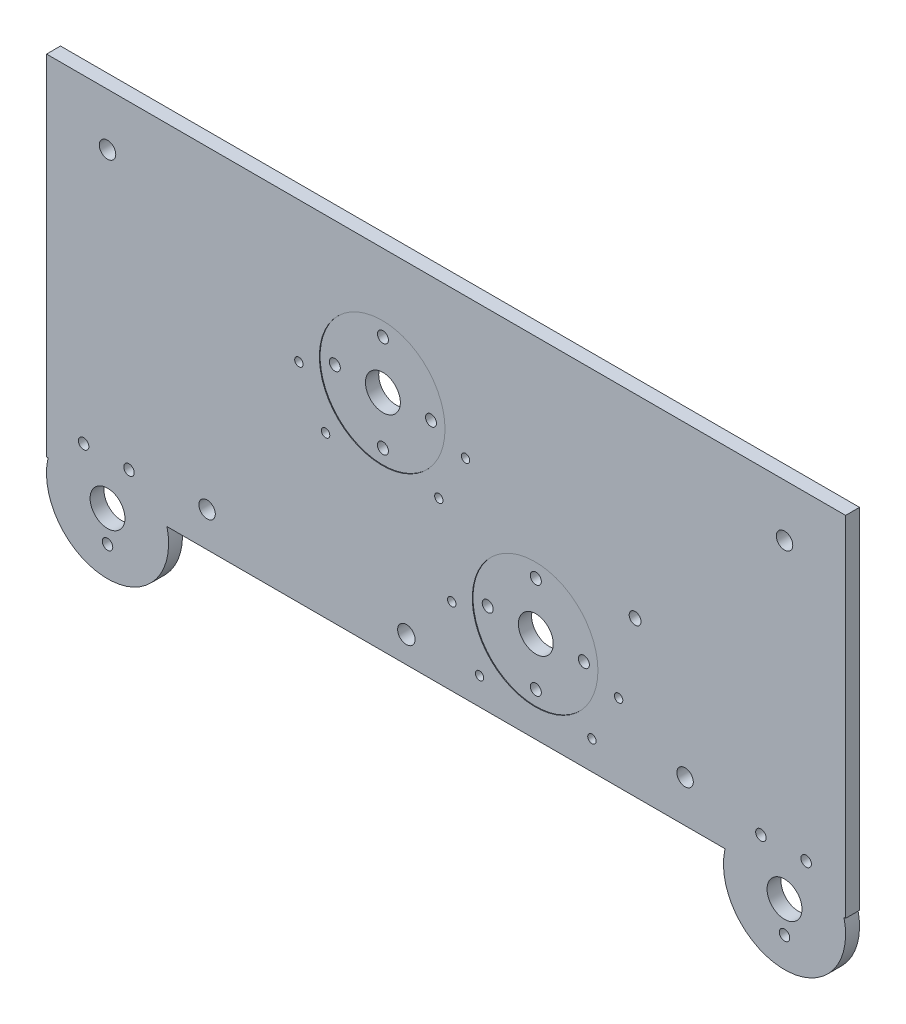
SolidWorks part; units mm, degrees
ref_plane "Front Plane" through (0, 0, 0) normal (0, 0, 1) x (1, 0, 0)
ref_plane "Top Plane" through (0, 0, 0) normal (0, 1, 0) x (1, 0, 0)
ref_plane "Right Plane" through (0, 0, 0) normal (1, 0, 0) x (0, 0, -1)
sketch "Sketch2" plane through (0, 0, 0) normal (0, 0, 1) x (1, 0, 0)
  line L1 (-143.383, -31.75) -> (143.383, -31.75)
  line L2 (-143.383, -31.75) -> (-143.383, 31.75)
  line L3 (-143.383, 31.75) -> (143.383, 31.75)
  line L4 (143.383, -31.75) -> (143.383, 31.75)
  line L5 (-143.383, -31.75) -> (143.383, 31.75) construction
  line L6 (-143.383, 31.75) -> (143.383, -31.75) construction
  line L16 (-143.383, 31.75) -> (143.383, 31.75)
  line L17 (-143.383, 31.75) -> (-143.383, 95.25)
  line L18 (-143.383, 95.25) -> (143.383, 95.25)
  line L19 (143.383, 31.75) -> (143.383, 95.25)
  circle A0 centre (-123.317, -36.83) radius 6.35
  circle A1 centre (123.063, -36.83) radius 6.35
  point P0 (0, 0)
  dimension "D3" = 20.066
  dimension "D5" = 5.08
  dimension "D7" = 63.5
  dimension "D4" = 12.7
  dimension "D1" = 63.5
  dimension "D2" = 286.766
  dimension "D6" = 20.32
extrude "Boss-Extrude1" add sketch "Sketch2" against normal blind 5.0749 contours A1 L1 L4 L3 L2 A0 | L3 L19 L18 L17 region at (0.0001, 0.0226, 0) region at (0, 63.5, 0)
ref_plane "Plane1" through (-143.383, 95.25, 0) normal (0, 1, 0) x (1, 0, 0)
ref_plane "Plane2" through (0, 0, -5.0749) normal (0, 0, -1) x (-1, 0, 0)
sketch "Sketch6" plane through (0, 0, -5.0749) normal (0, 0, -1) x (-1, 0, 0)
  line L0 (-116.713, -36.83) -> (-129.413, -36.83) construction
  line L1 (-123.063, -30.48) -> (-123.063, -43.18) construction
  line L3 (123.317, -30.48) -> (123.317, -43.18) construction
  line L4 (123.317, -43.18) -> (116.967, -36.83) construction
  line L6 (116.967, -36.83) -> (129.667, -36.83) construction
  circle A2 centre (-123.063, -36.83) radius 6.35 construction
  circle A3 centre (-123.063, -36.83) radius 22.225
  circle A4 centre (123.317, -36.83) radius 6.35 construction
  circle A5 centre (123.317, -36.83) radius 22.225
  dimension "D1" = 44.45
  dimension "D2" = 44.45
extrude "Boss-Extrude3" add sketch "Sketch6" against normal blind 5.0749
extrude "Cut-Extrude2" cut sketch "Sketch2<3>" against normal blind 5.588 contours A0 | A1
sketch "Sketch2<3>" plane through (0, 0, 0) normal (0, 0, 1) x (1, 0, 0) same geometry as "Sketch2"
sketch "Sketch8" plane through (0, 0, -5.0749) normal (0, 0, -1) x (-1, 0, 0)
  line L0 (145.5039, -31.75) -> (145.5039, 95.25) construction
  line L1 (198.383, 95.25) -> (88.383, 95.25) construction
  line L2 (143.383, -27.2746) -> (143.383, 95.25) construction
  line L3 (143.383, -31.75) -> (-143.383, -31.75) construction
  line L4 (145.5039, 95.25) -> (142.7757, 95.25)
  line L5 (145.5039, 95.25) -> (145.5039, -31.75)
  line L6 (145.5039, -31.75) -> (142.7757, -31.75)
  line L7 (142.7757, 95.25) -> (142.7757, -31.75)
  dimension "D1" = 2.1209
extrude "Boss-Extrude4" add sketch "Sketch8" against normal blind 5.0749
sketch "Sketch9" plane through (0, 0, -5.0749) normal (0, 0, -1) x (-1, 0, 0)
  line L0 (-145.288, -31.75) -> (-145.288, 5.0514) construction
  line L1 (-145.288, 95.25) -> (-143.383, 95.25)
  line L2 (-145.288, 95.25) -> (-145.288, -31.75)
  line L3 (-145.288, -31.75) -> (-143.383, -31.75)
  line L4 (-143.383, 95.25) -> (-143.383, -31.75)
  line L5 (-143.383, -31.75) -> (-143.383, 31.75) construction
  line L6 (143.383, 95.25) -> (-143.383, 95.25) construction
  line L7 (143.383, -31.75) -> (-143.383, -31.75) construction
extrude "Boss-Extrude5" add sketch "Sketch9" against normal blind 5.0749
sketch "Sketch12" plane through (0, 0, 0) normal (0, 0, 1) x (1, 0, 0)
  line L0 (-123.317, -43.18) -> (-123.317, 95.25) construction
  line L1 (-145.5039, 95.25) -> (145.288, 95.25) construction
  line L2 (-123.317, 95.25) -> (123.063, -43.18) construction
  line L3 (123.063, -43.18) -> (123.063, 95.25) construction
  line L4 (123.063, 95.25) -> (-123.317, -43.18) construction
  line L5 (-123.317, -43.18) -> (-123.317, 76.2) construction
  line L6 (-123.317, 76.2) -> (123.063, 76.2) construction
  circle A0 centre (-123.317, -36.83) radius 6.35 construction
  circle A1 centre (123.063, -36.83) radius 6.35 construction
  circle A2 centre (-123.317, 76.2) radius 3
  circle A3 centre (123.063, 76.2) radius 3
  dimension "D1" = 19.05
extrude "Cut-Extrude3" cut sketch "Sketch12" against normal blind 400.05
sketch "Sketch13" plane through (0, 0, -5.0749) normal (0, 0, -1) x (-1, 0, 0)
  line L0 (101.6804, -31.75) -> (-101.4264, -31.75) construction
  line L1 (145.5039, -31.75) -> (145.5039, 95.25) construction
  circle A0 centre (23.3525, 49.53) radius 22.86
  circle A1 centre (-32.2961, 1.27) radius 22.86
  circle A4 centre (-32.2961, 18.7706) radius 2
  circle A5 centre (-14.7955, 1.27) radius 2
  circle A6 centre (-32.2961, -16.2306) radius 2
  circle A7 centre (-49.7967, 1.27) radius 2
  circle A8 centre (23.3525, 67.0306) radius 2
  circle A9 centre (40.8531, 49.53) radius 2
  circle A10 centre (23.3525, 32.0294) radius 2
  circle A11 centre (5.8519, 49.53) radius 2
  circle A12 centre (-32.2961, 1.27) radius 6.35
  circle A13 centre (23.3525, 49.53) radius 6.35
  point P26 (0, 0)
  dimension "D1" = 81.28
  dimension "D3" = 177.8
  dimension "D4" = 45.72
  dimension "D6" = 17.5006
  dimension "D2" = 33.02
  dimension "D5" = 73.66
  dimension "D7" = 17.5006
  dimension "D8" = 17.5006
  dimension "D9" = 17.5006
  dimension "D10" = 17.5006
  dimension "D11" = 17.5006
  dimension "D12" = 17.5006
  dimension "D13" = 17.5006
extrude "Cut-Extrude4" cut sketch "Sketch13" along normal blind 0.254 from surface starting at face at (-120.317, 76.2, 0)
extrude "Cut-Extrude6" cut sketch "Sketch13<2>" against normal blind 127 contours A4 | A7 | A5 | A6 | A10 | A8 | A9 | A11 | A9 region at (32.2961, 18.7706, -5.0749) region at (14.7955, 1.27, -5.0749) region at (32.2961, -16.2306, -5.0749) region at (49.7967, 1.27, -5.0749) region at (-23.3525, 67.0306, -5.0749) region at (-40.8531, 49.53, -5.0749) region at (-23.3525, 32.0294, -5.0749) region at (-5.8519, 49.53, -5.0749)
sketch "Sketch13<2>" plane through (0, 0, -5.0749) normal (0, 0, -1) x (-1, 0, 0) same geometry as "Sketch13"
sketch "Sketch17" plane through (0, 0, -5.0749) normal (0, 0, -1) x (-1, 0, 0)
  line L0 (145.5039, -31.75) -> (145.5039, 95.25) construction
  line L2 (101.6804, -31.75) -> (-101.4264, -31.75) construction
  circle A0 centre (-86.868, -16.51) radius 2.9972
  circle A1 centre (87.0839, -19.05) radius 2.9972
  dimension "D1" = 58.42
  dimension "D3" = 15.24
  dimension "D4" = 12.7
extrude "Cut-Extrude7" cut sketch "Sketch17" against normal blind 152.4 contours A1 | A0 | A0 region at (86.868, -16.51, -5.0749) region at (-87.0839, -19.05, -5.0749)
extrude "Cut-Extrude8" cut sketch "Sketch13<3>" against normal blind 1549.4 contours A12 | A13 region at (32.2961, 1.27, -5.0749) region at (-23.3525, 49.53, -5.0749)
sketch "Sketch13<3>" plane through (0, 0, -5.0749) normal (0, 0, -1) x (-1, 0, 0) same geometry as "Sketch13"
sketch "Sketch18" plane through (0, 0, -5.0749) normal (0, 0, -1) x (-1, 0, 0)
  line L0 (145.5039, -35.5292) -> (14.5669, -35.5292) construction
  line L1 (14.5669, -31.75) -> (14.5669, -22.225) construction
  line L2 (101.6804, -31.75) -> (-101.4264, -31.75) construction
  line L3 (-145.288, 24.511) -> (-68.692, 24.511) construction
  line L5 (-68.692, 24.511) -> (-68.692, -31.75) construction
  line L6 (-52.9623, -31.75) -> (-52.9623, -21.3216) construction
  line L7 (-62.6821, -3.6208) -> (-1.9537, -3.6208) construction
  line L8 (-32.2961, -29.464) -> (-32.5153, -21.5953) construction
  line L9 (-145.288, -21.3216) -> (-50.292, -21.3216) construction
  line L10 (-52.9623, -21.3216) -> (-12.0683, -21.869) construction
  line L11 (23.3525, 18.7252) -> (23.3525, 26.6295) construction
  line L12 (2.749, 26.6295) -> (43.956, 26.6295) construction
  line L13 (43.956, 26.6295) -> (53.6778, 44.1159) construction
  line L14 (53.6778, 44.1159) -> (-6.9728, 44.1159) construction
  circle A0 centre (14.5669, -22.225) radius 3.175
  circle A1 centre (-68.692, 24.511) radius 2.159
  circle A2 centre (-62.6821, -3.6208) radius 1.524
  circle A4 centre (-32.2961, 1.27) radius 30.734
  circle A5 centre (-1.9537, -3.6208) radius 1.524
  circle A6 centre (-12.0683, -21.869) radius 1.524
  circle A7 centre (-52.9623, -21.3216) radius 1.524
  circle A8 centre (23.3525, 49.53) radius 30.8048
  circle A9 centre (-6.9728, 44.1159) radius 1.524
  circle A10 centre (2.749, 26.6295) radius 1.524
  circle A11 centre (43.956, 26.6295) radius 1.524
  circle A12 centre (53.6778, 44.1159) radius 1.524
  dimension "D1" = 56.261
  dimension "D2" = 94.996
  dimension "D3" = 61.468
  dimension "D4" = 40.894
  dimension "D6" = 7.9043
  dimension "D5" = 17.7008
  dimension "D7" = 17.4864
extrude "Cut-Extrude9" cut sketch "Sketch18" against normal blind 6.35 contours A1 | A4 A2 | A2 A4 | A4 A7 | A4 A7 | A4 A6 | A4 A6 | A4 A5 | A4 A5 | A0 | A8 A9 | A8 A9 | A8 A10 | A8 A10 | A8 A11 | A8 A11 | A8 A12 | A8 A12 region at (-14.5669, -22.225, -5.0749) region at (68.692, 24.511, -5.0749) region at (62.0138, -3.5133, -5.0749) region at (63.291, -3.7188, -5.0749) region at (52.5631, -20.8853, -5.0749) region at (53.4367, -21.8402, -5.0749) region at (1.3219, -3.7227, -5.0749) region at (2.599, -3.5168, -5.0749) region at (12.4984, -21.3769, -5.0749) region at (11.6471, -22.3508, -5.0749) region at (6.3294, 44.2308, -5.0749) region at (7.6028, 44.0034, -5.0749) region at (-54.3078, 44.0034, -5.0749) region at (-53.0344, 44.2308, -5.0749) region at (-3.1861, 27.1154, -5.0749) region at (-2.321, 26.1538, -5.0749) region at (-44.384, 26.1538, -5.0749) region at (-43.5189, 27.1154, -5.0749)
sketch "Sketch19" plane through (0, 0, -5.0749) normal (0, 0, -1) x (-1, 0, 0)
  line L0 (-123.063, -59.055) -> (-123.063, -48.133) construction
  line L1 (-123.063, -48.133) -> (-114.4581, -20.8844) construction
  line L2 (-145.288, -20.8844) -> (-130.937, -20.8844) construction
  line L4 (-130.937, -20.8844) -> (-114.4581, -20.8844) construction
  line L5 (-130.937, -20.8844) -> (-123.063, -48.133) construction
  line L6 (123.317, -59.055) -> (123.317, -48.133) construction
  line L7 (123.317, -48.133) -> (115.5016, -20.7796) construction
  line L8 (115.5016, -20.7796) -> (132.0116, -20.7796) construction
  line L9 (132.0116, -20.7796) -> (123.317, -48.133) construction
  arc A0 (-144.6996, -31.75) -> (-101.4264, -31.75) centre (-123.063, -36.83) ccw construction
  circle A1 centre (-130.937, -20.8844) radius 1.905
  circle A2 centre (-114.4581, -20.8844) radius 1.905
  circle A3 centre (-123.063, -48.133) radius 1.905
  arc A4 (101.6804, -31.75) -> (144.9536, -31.75) centre (123.317, -36.83) ccw construction
  circle A5 centre (115.5016, -20.7796) radius 1.905
  circle A6 centre (132.0116, -20.7796) radius 1.905
  circle A7 centre (123.317, -48.133) radius 1.905
  dimension "D4" = 10.922
  dimension "D1" = 28.575
  dimension "D2" = 14.351
  dimension "D3" = 16.4789
  dimension "D5" = 10.922
  dimension "D6" = 16.51
  dimension "D7" = 28.702
  dimension "D8" = 28.448
extrude "Cut-Extrude10" cut sketch "Sketch19" against normal blind 6.35
